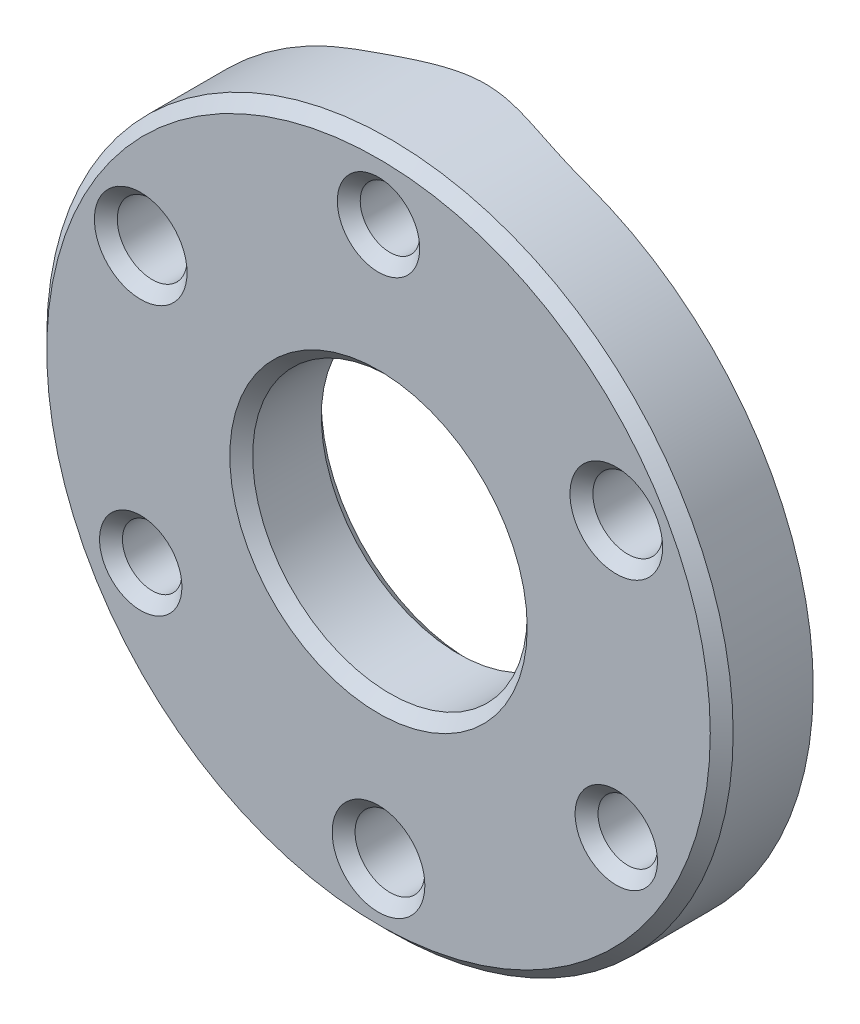
SolidWorks part; units mm, degrees
material "ABS"
ref_plane "前视基准面" through (0, 0, 0) normal (0, 0, 1) x (1, 0, 0)
ref_plane "上视基准面" through (0, 0, 0) normal (0, 1, 0) x (1, 0, 0)
ref_plane "右视基准面" through (0, 0, 0) normal (1, 0, 0) x (0, 0, -1)
other "Configuration Table"
sketch "草图1" plane through (0, 0, 0) normal (0, 0, 1) x (1, 0, 0)
  line L0 (0, 0) -> (0, 20) construction
  line L1 (0, 20) -> (0, 33) construction
  line L2 (0, 33) -> (13.3609, 6.8182)
  line L3 (0, 33) -> (-13.3609, 6.8182)
  line L4 (0, 0) -> (0, -15) construction
  line L5 (10.3923, -6) -> (0, 0) construction
  circle A0 centre (0, 0) radius 15 construction
  circle A1 centre (0, 20) radius 1.55
  arc A2 (-13.3609, 6.8182) -> (13.3609, 6.8182) centre (0, 0) ccw
  circle A3 centre (0, 0) radius 12 construction
  circle A5 centre (10.3923, -6) radius 1.3
  circle A6 centre (-10.3923, -6) radius 1.3
  circle A7 centre (0, 12) radius 1.3
  dimension "D1" = 30
  dimension "D3" = 3.1
  dimension "D5" = 24
  dimension "D6" = 2.6
  dimension "D2" = 20
  dimension "D4" = 13
  dimension "D7" = 60
  dimension "D8" = 3
extrude "凸台-拉伸1" add sketch "草图1" along normal blind 3
sketch "草图4" plane through (0, 0, 3) normal (0, 0, 1) x (1, 0, 0)
  line L0 (10.3923, 6) -> (0, 0) construction
  line L1 (0, 0) -> (15, 0) construction
  circle A0 centre (0, 0) radius 15
  circle A1 centre (10.3923, 6) radius 1.525
  circle A2 centre (0, -12) radius 1.525
  circle A3 centre (-10.3923, 6) radius 1.525
  dimension "D1" = 30
  dimension "D2" = 3.05
  dimension "D3" = 30
  dimension "D4" = 12
  dimension "D5" = 3
extrude "凸台-拉伸3" add sketch "草图4" along normal blind 1
sketch "草图2" plane through (0, 0, 3) normal (0, 0, 1) x (1, 0, 0)
  circle A1 centre (10.3923, -6) radius 1.3
  circle A2 centre (0, 12) radius 1.3
  circle A3 centre (-10.3923, -6) radius 1.3
  circle A4 centre (0, 0) radius 6
  dimension "D1" = 2.6
  dimension "D2" = 12
  dimension "D3" = 2.6
  dimension "D4" = 2.6
extrude "切除-拉伸2" cut sketch "草图2" against normal through all and the other way through all
fillet "圆角4" radius 6 1 edges at (0, 33, 1.5)
sketch "草图5" plane through (0, 0, 4) normal (0, 0, 1) x (1, 0, 0)
  circle A2 centre (0, -12) radius 1.525
  circle A3 centre (10.3923, 6) radius 1.525
  circle A4 centre (-10.3923, 6) radius 1.525
  dimension "D1" = 3.05
  dimension "D2" = 3.05
  dimension "D3" = 3.05
extrude "切除-拉伸3" cut sketch "草图5" against normal blind 4
sketch "草图6" plane through (0, 0, 4) normal (0, 0, 1) x (1, 0, 0)
  circle A0 centre (0, 0) radius 15
  dimension "D1" = 30
extrude "切除-拉伸4" cut sketch "草图6" against normal blind 10 flip side to cut
chamfer "倒角2" distance 1.1 angle 45 2 edges at (-9.0923, -6, 0) (11.6923, -6, 0)
sketch "草图7" plane through (0, 0, 0) normal (0, 0, -1) x (-1, 0, 0)
  circle A0 centre (0, 12) radius 1.3
  circle A1 centre (0, 12) radius 2.5
  dimension "D1" = 2.6
  dimension "D2" = 5
extrude "凸台-拉伸4" add sketch "草图7" along normal blind 1
fillet "圆角5" radius 5 1 edges at (2.5, 12, 0)
chamfer "倒角3" distance 0.5 angle 45 12 edges at (-8.8673, 6, 4) (11.9173, 6, 4) (15, 0, 4) (1.525, -12, 4) (1.3, 12, 4) (-9.0923, -6, 4) (11.6923, -6, 4) (6, 0, 4) (6, 0, 0) (1.525, -12, 0) (-8.8673, 6, 0) (11.9173, 6, 0)
